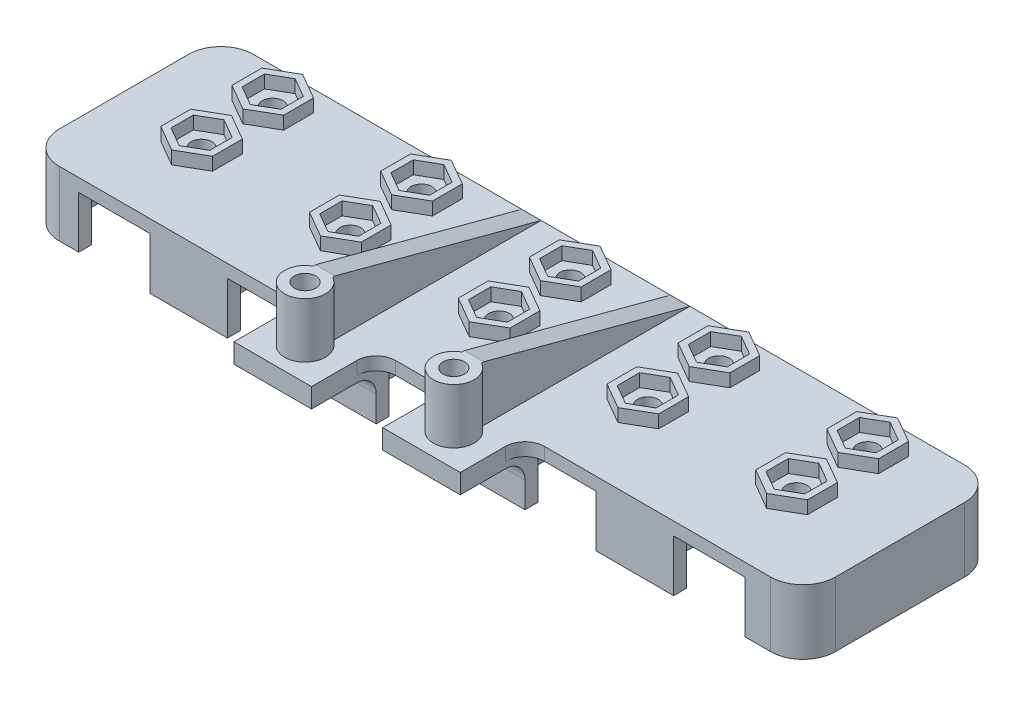
SolidWorks part; units mm, degrees
material "ABS"
ref_plane "Front Plane" through (0, 0, 0) normal (0, 0, 1) x (1, 0, 0)
ref_plane "Top Plane" through (0, 0, 0) normal (0, 1, 0) x (1, 0, 0)
ref_plane "Right Plane" through (0, 0, 0) normal (1, 0, 0) x (0, 0, -1)
sketch "Sketch1" plane through (0, 0, 0) normal (0, 1, 0) x (1, 0, 0)
  line L0 (-46.5, 13) -> (-46.5, -29) construction
  line L1 (-55, -15) -> (55, -15)
  line L2 (-60, -10) -> (-60, 10)
  line L3 (-55, 15) -> (55, 15)
  line L4 (60, -10) -> (60, 10)
  line L5 (-60, -15) -> (60, 15) construction
  line L6 (-60, 15) -> (60, -15) construction
  line L7 (-52, -29) -> (-41, -29)
  line L8 (-52, -29) -> (-52, 13)
  line L9 (-52, 13) -> (-41, 13)
  line L10 (-41, -29) -> (-41, 13)
  line L11 (-52, -29) -> (-41, 13) construction
  line L12 (-52, 13) -> (-41, -29) construction
  line L13 (-46.5, 3.1188) -> (-50.5, 0.8094)
  line L14 (-41, 13) -> (-36, 13)
  line L15 (-41, 13) -> (-41, -13)
  line L16 (-41, -13) -> (-36, -13)
  line L17 (-36, 13) -> (-36, -13)
  line L18 (-52, 13) -> (-57, 13)
  line L19 (-52, 13) -> (-52, -13)
  line L20 (-52, -13) -> (-57, -13)
  line L21 (-57, 13) -> (-57, -13)
  line L22 (-46.5, 1.9641) -> (-49.5, 0.2321)
  line L23 (-49.5, 0.2321) -> (-49.5, -3.2321)
  line L24 (-49.5, -3.2321) -> (-46.5, -4.9641)
  line L25 (-46.5, -4.9641) -> (-43.5, -3.2321)
  line L26 (-43.5, -3.2321) -> (-43.5, 0.2321)
  line L27 (-43.5, 0.2321) -> (-46.5, 1.9641)
  line L28 (-46.5, 6.0359) -> (-43.5, 7.7679)
  line L29 (-43.5, 7.7679) -> (-43.5, 11.2321)
  line L30 (-43.5, 11.2321) -> (-46.5, 12.9641)
  line L31 (-46.5, 12.9641) -> (-49.5, 11.2321)
  line L32 (-49.5, 11.2321) -> (-49.5, 7.7679)
  line L33 (-49.5, 7.7679) -> (-46.5, 6.0359)
  line L34 (-50.5, 0.8094) -> (-50.5, -3.8094)
  line L35 (-50.5, -3.8094) -> (-46.5, -6.1188)
  line L36 (-46.5, -6.1188) -> (-42.5, -3.8094)
  line L37 (-42.5, -3.8094) -> (-42.5, 0.8094)
  line L38 (-42.5, 0.8094) -> (-46.5, 3.1188)
  line L39 (-46.5, 4.8812) -> (-42.5, 7.1906)
  line L40 (-42.5, 7.1906) -> (-42.5, 11.8094)
  line L41 (-42.5, 11.8094) -> (-46.5, 14.1188)
  line L42 (-46.5, 14.1188) -> (-50.5, 11.8094)
  line L43 (-50.5, 11.8094) -> (-50.5, 7.1906)
  line L44 (-50.5, 7.1906) -> (-46.5, 4.8812)
  arc A0 (55, 15) -> (60, 10) centre (55, 10) cw
  arc A1 (-60, 10) -> (-55, 15) centre (-55, 10) cw
  arc A2 (-60, -10) -> (-55, -15) centre (-55, -10) ccw
  arc A3 (60, -10) -> (55, -15) centre (55, -10) cw
  circle A4 centre (-46.5, 9.5) radius 1.6
  circle A5 centre (-46.5, -1.5) radius 1.6
  circle A6 centre (-46.5, -1.5) radius 4 construction
  circle A7 centre (-46.5, 9.5) radius 4 construction
  circle A8 centre (-46.5, -1.5) radius 3 construction
  circle A9 centre (-46.5, 9.5) radius 3 construction
  point P0 (0, 0)
  point P9 (-46.5, -8)
  dimension "D1" = 5
  dimension "D2" = 11
  dimension "D3" = 42
  dimension "D4" = 2
  dimension "D5" = 30
  dimension "D7" = 3.2
  dimension "D8" = 3.2
  dimension "D14" = 6
  dimension "D15" = 6
  dimension "D6" = 120
  dimension "D9" = 3.5
  dimension "D10" = 11
  dimension "D11" = 13.5
  dimension "D12" = 5
  dimension "D13" = 2
  dimension "D16" = 1
  dimension "D17" = 1
extrude "Boss-Extrude1" add sketch "Sketch1" along normal blind 10 contours L3 A0 L4 A3 L1 A2 L2 A1
extrude "Cut-Extrude3" cut sketch "Sketch1<5>" along normal blind 6 contours L21 A2 L1 L8 L18 | L17 L14 L10 L1 region at (-54.5, 0, 0) region at (-38.5, 0, 0)
sketch "Sketch1<5>" plane through (0, 0, 0) normal (0, 1, 0) x (1, 0, 0) same geometry as "Sketch1"
extrude "Boss-Extrude2" add sketch "Sketch1<8>" along normal blind 2 from surface contours L43 L44 L39 L40 L41 L9 L30 L29 L28 L33 L32 L31 L42 | L41 L42 L9 L31 L30 | L37 L38 L13 L34 L35 L36 L27 L26 L25 L24 L23 L22 region at (-46.5, 0, -13.3729) region at (-46.5, 0, -12.9886) region at (-44.5611, 0, -1.8583) starting at face at (0, 10, 0)
sketch "Sketch1<8>" plane through (0, 0, 0) normal (0, 1, 0) x (1, 0, 0) same geometry as "Sketch1"
extrude "Cut-Extrude4" cut sketch "Sketch1<9>" along normal blind 8 contours L44 L43 L42 L9 L8 L1 L10 L41 L40 L39 L38 L37 L36 L35 L34 L13 | L7 L10 L1 L8 | L37 L38 L13 L34 L35 L36 L27 L26 L25 L24 L23 L22 | L26 L27 L22 L23 L24 L25 A5 | A5 | L32 L33 L28 L29 L30 L9 L31 A4 | L43 L44 L39 L40 L41 L9 L30 L29 L28 L33 L32 L31 L42 | A4 region at (-51.6992, 0, 14) region at (-46.5, 0, 22) region at (-46.5, 0, -12.9886) region at (-44.5611, 0, -1.8583) region at (-45.0458, 0, -1.0187) region at (-47.9542, 0, -6.9813) region at (-46.5, 0, -9.5) region at (-46.5, 0, 1.5)
sketch "Sketch1<9>" plane through (0, 0, 0) normal (0, 1, 0) x (1, 0, 0) same geometry as "Sketch1"
extrude "Cut-Extrude5" cut sketch "Sketch1<10>" along normal up to next contours A4 | A5
sketch "Sketch1<10>" plane through (0, 0, 0) normal (0, 1, 0) x (1, 0, 0) same geometry as "Sketch1"
pattern_linear "LPattern4" count 5 spacing 23 along (1, 0, 0) of "Cut-Extrude5", "Cut-Extrude4", "Boss-Extrude2", "Cut-Extrude3"
sketch "Sketch4" plane through (0, 10, 0) normal (0, 1, 0) x (1, 0, 0)
  line L0 (-0.5, -15) -> (-0.5, -25) construction
  line L1 (5, -25) -> (17, -25)
  line L2 (5, -25) -> (5, -15)
  line L3 (5, -15) -> (17, -15)
  line L4 (17, -25) -> (17, -15)
  line L5 (5, -25) -> (17, -15) construction
  line L6 (5, -15) -> (17, -25) construction
  line L7 (-6, -15) -> (5, -15) construction
  line L8 (-6, -15) -> (-18, -25) construction
  line L9 (-6, -25) -> (-18, -15) construction
  line L10 (-18, -25) -> (-18, -15)
  line L11 (-6, -15) -> (-18, -15)
  line L12 (-6, -25) -> (-6, -15)
  line L13 (-6, -25) -> (-18, -25)
  point P0 (11, -20)
  dimension "D3" = 10
extrude "Boss-Extrude3" add sketch "Sketch4" against normal blind 3 contours L1 L4 L3 L2 | L10 L11 L12 L13 region at (11, 10, 20)
fillet "Fillet2" radius 3 6 edges at (17, 9, 15) (5, 9, 15) (11, 7, 15) (-12, 7, 15) (-18, 9, 15) (-6, 9, 15)
sketch "Sketch5" plane through (0, 10, 0) normal (0, 1, 0) x (1, 0, 0)
  line L1 (11, -10) -> (11, -20) construction
  line L3 (-12, -10) -> (-12, -20) construction
  line L5 (11, -15) -> (-12, -15) construction
  line L6 (-6, -25) -> (-18, -25) construction
  line L7 (5, -25) -> (17, -25) construction
  circle A0 centre (11, -10) radius 1.65
  circle A1 centre (-12, -10) radius 1.65
  circle A2 centre (11, -10) radius 3.15
  circle A3 centre (-12, -10) radius 3.15
  circle A4 centre (-12, -20) radius 3.15
  circle A5 centre (11, -20) radius 3.15
  circle A6 centre (-12, -20) radius 1.65
  circle A7 centre (11, -20) radius 1.65
  point P12 (-12, -25)
  point P26 (11, -25)
  dimension "D1" = 3.3
  dimension "D2" = 1.5
  dimension "D3" = 10
  dimension "D4" = 10
extrude "Boss-Extrude5" add sketch "Sketch5" along normal blind 8.5 contours A4 | A5
extrude "Cut-Extrude6" cut sketch "Sketch5<3>" along normal through all both and the other way through all contours A7 | A6
sketch "Sketch5<3>" plane through (0, 10, 0) normal (0, 1, 0) x (1, 0, 0) same geometry as "Sketch5"
ref_plane "Plane1" through (11, 0, 0) normal (1, 0, 0) x (0, 0, -1)
sketch "Sketch6" plane through (11, 0, 0) normal (1, 0, 0) x (0, 0, -1)
  line L0 (15, 10) -> (-16.85, 18.5)
  line L1 (-16.85, 10) -> (-16.85, 18.5) construction
  line L3 (-16.85, 18.5) -> (-17.85, 18.5)
  line L4 (-16.85, 18.5) -> (-16.85, 9)
  line L5 (-16.85, 9) -> (-17.85, 9)
  line L6 (-17.85, 18.5) -> (-17.85, 9)
  line L7 (15, 10) -> (-17.85, 10)
  line L8 (15, 10) -> (15, 9)
  line L9 (15, 9) -> (-17.85, 9)
  line L10 (-17.85, 10) -> (-17.85, 9)
  dimension "D1" = 1
  dimension "D2" = 1
extrude "Boss-Extrude6" add sketch "Sketch6" along normal mid plane 3 contours L7 L0 L4 | L7 L4 L3 L6 | L9 L8 L7 L4 | L4 L7 L6 L5 region at (11, 12.8333, 6.2333) region at (11, 9.5, 0.925) region at (11, 14.25, 17.35) region at (11, 9.5, 17.35)
ref_plane "Plane2" through (-12, 0, 0) normal (1, 0, 0) x (0, 0, -1)
sketch "Sketch7" plane through (-12, 0, 0) normal (1, 0, 0) x (0, 0, -1)
  line L0 (15, 10) -> (-17.85, 10) construction
  line L1 (15, 10) -> (15, 9) construction
  line L2 (-16.85, 18.5) -> (-17.85, 18.5) construction
  line L3 (15, 10) -> (-16.85, 18.5) construction
  line L4 (-16.85, 18.5) -> (-16.85, 9) construction
  line L5 (-17.85, 18.5) -> (-17.85, 9) construction
  line L6 (15, 9) -> (-17.85, 9) construction
  line L7 (15, 10) -> (-17.85, 10)
  line L8 (15, 10) -> (15, 9)
  line L9 (-16.85, 18.5) -> (-17.85, 18.5)
  line L10 (15, 10) -> (-16.85, 18.5)
  line L11 (-16.85, 18.5) -> (-16.85, 9)
  line L12 (-17.85, 18.5) -> (-17.85, 9)
  line L13 (15, 9) -> (-17.85, 9)
extrude "Boss-Extrude7" add sketch "Sketch7" along normal mid plane 3 contours L10 L11 L7 | L9 L12 L7 L11 | L13 L8 L7 L11 | L13 L11 L7 L12 region at (-12, 9.5, 0.925) region at (-12, 12.8333, 6.2333) region at (-12, 9.5, 17.35) region at (-12, 14.25, 17.35)
